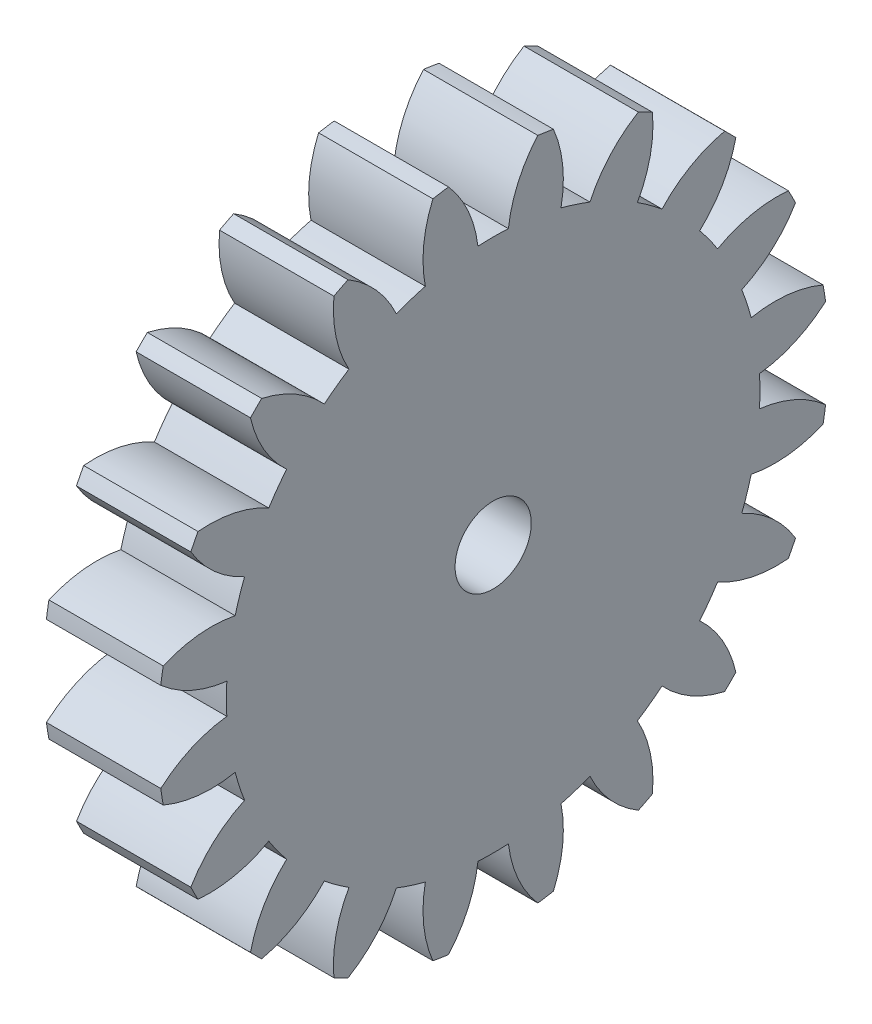
SolidWorks part; units mm, degrees
ref_plane "Plane1" through (0, 0, 0) normal (0, 0, 1) x (1, 0, 0)
ref_plane "Plane2" through (0, 0, 0) normal (0, 1, 0) x (1, 0, 0)
ref_plane "Plane3" through (0, 0, 0) normal (1, 0, 0) x (0, 0, -1)
sketch "HoldingSke" plane through (0, 0, 0) normal (0, 1, 0) x (1, 0, 0)
  line L0 (0, 0) -> (119.341, -43.4366)
  line L1 (-15, 0) -> (100, 0) construction
  line L2 (0, 0) -> (-2.1039, 2.3779)
  line L3 (0, 0) -> (-11.863, 4.5341)
  line L4 (0, 0) -> (8.1152, 2.9537)
  line L5 (0, 0) -> (-47.5972, -17.7524)
  line L6 (0, 0) -> (-15.7917, -10.6547)
  line L7 (-2.1039, 2.3779) -> (8.8308, 51.9871)
  line L8 (-76.2, 54.61) -> (-61.976, 54.61)
  line L9 (-71.009, 38.7566) -> (-53.1078, 45.2721)
  line L10 (-76.2, 71.12) -> (104.1128, 71.12)
  line L11 (0, 0) -> (-19.05, 0)
  line L12 (-76.2, 101.6) -> (-76.0095, 101.6)
  line L13 (24.9733, 27.94) -> (52.9518, 28.4284)
  line L14 (24.9733, 27.94) -> (24.9746, 27.94)
  line L15 (24.9733, 27.94) -> (100.4006, 29.5858)
  circle A0 centre (0, 0) radius 6.35
  circle A1 centre (0, 0) radius 38.1
  circle A2 centre (0, 0) radius 38.1
  circle A3 centre (0, 0) radius 6.35
  dimension "Num_teeth" = 20
  dimension "H" = 19.05
  dimension "Pitch_radius" = 180.3128
  dimension "Width" = 19.05
  dimension "Thickness" = 19.05
sketch "BasProSke" plane through (0, 0, 0) normal (0, 1, 0) x (1, 0, 0)
  line L0 (-10, 0) -> (60, 0) construction
  line L1 (0, 0) -> (0, 55.88)
  line L2 (0, 0) -> (19.05, 0)
  line L3 (19.05, 0) -> (19.05, 55.88)
  line L4 (19.05, 55.88) -> (0, 55.88)
  dimension "Thickness" = 19.05
  dimension "Diameter" = 111.76
revolve "Base-Revolve" add sketch "BasProSke" angle 360 about L0
sketch "TooCutSke" plane through (0, 0, 0) normal (1, 0, 0) x (0, 0, -1)
  line L1 (0, 0) -> (0, 107) construction
  line L2 (0, 0) -> (-4.3189, 50.6161) construction
  line L3 (0, 0) -> (-15.8526, 100.0894) construction
  line L4 (-4.3189, 50.6161) -> (-7.9263, 50.0447) construction
  arc A0 (2.5362, 44.3763) -> (-2.5362, 44.3763) centre (0, 0) ccw
  arc A1 (7.4573, 55.4058) -> (-7.4573, 55.4058) centre (0, 0) ccw
  circle A2 centre (0, 0) radius 50.8 construction
  circle A3 centre (0, 0) radius 47.7364 construction
  arc A4 (-2.5362, 44.3763) -> (-7.4573, 55.4058) centre (-22.715, 41.9856) ccw
  arc A5 (7.4573, 55.4058) -> (2.5362, 44.3763) centre (22.715, 41.9856) ccw
extrude "ToothCut" cut sketch "TooCutSke" along normal through all
fillet "Breaks" [suppressed] radius 0.1016 tangent propagation no
fillet "RootFillets" [suppressed] radius 1.2713
pattern_circular "TeethCuts" count 20 every 18 about axis through (-10, 0, 0) along (1, 0, 0) of "ToothCut", "RootFillets", "Breaks"
sketch "HubNeaOneSke" plane through (0, 0, 0) normal (-1, 0, 0) x (0, 0, 1)
  circle A0 centre (0, 0) radius 38.1
  dimension "Diameter" = 76.2
extrude "HubNearOne" [suppressed] add sketch "HubNeaOneSke" along normal blind 31.7501
sketch "HubNeaBotSke" plane through (0, 0, 0) normal (-1, 0, 0) x (0, 0, 1)
  circle A0 centre (0, 0) radius 38.1
  dimension "Diameter" = 76.2
extrude "HubNearBoth" [suppressed] add sketch "HubNeaBotSke" along normal blind 15.875
ref_plane "FarPln" through (19.05, 0, 0) normal (1, 0, 0) x (0, 0, -1)
sketch "HubFarSke" plane through (19.05, 0, 0) normal (1, 0, 0) x (0, 0, -1)
  circle A0 centre (0, 0) radius 38.1
  dimension "Diameter" = 76.2
extrude "HubFar" [suppressed] add sketch "HubFarSke" along normal blind 15.875
sketch "BorSke" plane through (0, 0, 0) normal (1, 0, 0) x (0, 0, -1)
  circle A0 centre (0, 0) radius 6.35
  dimension "Diameter" = 12.7
extrude "Bore" cut sketch "BorSke" along normal mid plane 101.6001
sketch "KeySke" plane through (0, 0, 0) normal (1, 0, 0) x (0, 0, -1)
  line L0 (-1.5875, 0) -> (-1.5875, 7.874)
  line L1 (-1.5875, 7.874) -> (1.5875, 7.874)
  line L2 (1.5875, 7.874) -> (1.5875, 0)
  line L3 (0, 0) -> (0, 34) construction
  line L4 (-1.5875, 0) -> (1.5875, 0)
  dimension "Width" = 3.175
extrude "Keyway" [suppressed] cut sketch "KeySke" along normal mid plane 101.6001
pattern_circular "Keyway2" [suppressed] count 2 every 90 about axis through (-10, 0, 0) along (1, 0, 0) reverse direction yes
equation "' \"Pitch@HoldingSke\" = 4"
equation "' \"Num_teeth@HoldingSke\" = 12"
equation "' \"Ap@HoldingSke\" =  20"
equation "' \"Ap@HoldingSke\" = 20"
equation "' \"Width@HoldingSke\" = 0.5"
equation "' \"Hub_dia@HoldingSke\"= 1"
equation "' \"Hub_dia@HoldingSke\" = 1"
equation "' \"Overall_len@HoldingSke\" = 1.0"
equation "' \"Bore@HoldingSke\" = 0.75"
equation "' \"T_dim@HoldingSke\" = 0.85"
equation "' \"Width@KeySke\" = 0.25"
equation "' \"Show_teeth@HoldingSke\" = 13"
equation "' \"Backlash@HoldingSke\" = 0.009"
equation "' \"Addendum_fac@HoldingSke\" = 1.0"
equation "' \"Dedendum_fac@HoldingSke\" = 1.25"
equation "' \"Dedendum_add@HoldingSke\" = 0.00005"
equation "' \"Clearance_fac@HoldingSke\" = 0.25"
equation "' \"Pitch@HoldingSke\" = 0.5"
equation "' \"Num_teeth@HoldingSke\" = 23"
equation "' \"Show_teeth@HoldingSke\" = 23"
equation "' \"Backlash@HoldingSke\" = 0.0375"
equation "\"Overcut_dia@TooCutSke\" = (\"Num_teeth@HoldingSke\" + 2 * \"Addendum_fac@HoldingSke\") / \"Pitch@HoldingSke\" + 0.002"
equation "\"Pitch_dia@TooCutSke\" = \"Num_teeth@HoldingSke\" / \"Pitch@HoldingSke\""
equation "\"Base_dia@TooCutSke\" = \"Num_teeth@HoldingSke\" / \"Pitch@HoldingSke\" * cos((\"Ap@HoldingSke\"  * 3.14159265 / 180))"
equation "\"Root_dia@TooCutSke\" = (\"Num_teeth@HoldingSke\" + 2) / \"Pitch@HoldingSke\" - 2 * (\"Addendum_fac@HoldingSke\" + \"Dedendum_fac@HoldingSke\") / \"Pitch@HoldingSke\" - \"Dedendum_add@HoldingSke\" * 2"
equation "\"Half_ang@TooCutSke\" = 180 / \"Num_teeth@HoldingSke\""
equation "\"Half_CT@TooCutSke\" = \"Num_teeth@HoldingSke\" / \"Pitch@HoldingSke\" * sin((3.14159265 / 2 / \"Num_teeth@HoldingSke\")) / 2 - 7 * \"Backlash@HoldingSke\" / 4"
equation "\"Flank_rad@TooCutSke\" = \"Num_teeth@HoldingSke\" / \"Pitch@HoldingSke\" / 5"
equation "\"Radius@RootFillets\" = \"Clearance_fac@HoldingSke\" / \"Pitch@HoldingSke\" + \"Dedendum_add@HoldingSke\""
equation "\"Break_rad@Breaks\" = 0.02 / \"Pitch@HoldingSke\""
equation "\"Thickness@HoldingSke\" = \"Width@HoldingSke\""
equation "\"OAL@HoldingSke\" = \"Thickness@HoldingSke\""
equation "\"MHD@HoldingSke\" = (\"Num_teeth@HoldingSke\" + 2) / \"Pitch@HoldingSke\" - 2 * (\"Addendum_fac@HoldingSke\" + \"Dedendum_fac@HoldingSke\")  / \"Pitch@HoldingSke\" - \"Dedendum_add@HoldingSke\" * 2"
equation "\"MBD@HoldingSke\" = (\"Num_teeth@HoldingSke\" + 2) / \"Pitch@HoldingSke\" - 2 * (\"Addendum_fac@HoldingSke\" + \"Dedendum_fac@HoldingSke\")  / \"Pitch@HoldingSke\" - \"Dedendum_add@HoldingSke\" * 2 - 0.002"
equation "\"MHD@HoldingSke\" = ((sgn( \"MHD@HoldingSke\" - \"Hub_dia@HoldingSke\" )-1)*( \"MHD@HoldingSke\" - \"Hub_dia@HoldingSke\" ))/-2+ \"Hub_dia@HoldingSke\""
equation "\"MBD@HoldingSke\" = ((sgn( \"MBD@HoldingSke\" - \"Bore@HoldingSke\" )-1)*( \"MBD@HoldingSke\" - \"Bore@HoldingSke\" ))/-2+ \"Bore@HoldingSke\""
equation "\"OAL@HoldingSke\" = ((sgn( \"OAL@HoldingSke\" - \"Overall_len@HoldingSke\" )+1)*( \"OAL@HoldingSke\" - \"Overall_len@HoldingSke\" ))/2 + \"Overall_len@HoldingSke\" + 0.000002"
equation "\"Num_teeth@TeethCuts\" = int( \"Show_teeth@HoldingSke\" ) + 1"
equation "\"Num_teeth@TeethCuts\" = ((sgn( \"Num_teeth@TeethCuts\" - \"Num_teeth@HoldingSke\" )-1)*( \"Num_teeth@TeethCuts\" - \"Num_teeth@HoldingSke\" ))/-2+ \"Num_teeth@HoldingSke\""
equation "\"Num_teeth@TeethCuts\" = ((sgn( \"Num_teeth@TeethCuts\" - 2.0)+1)*( \"Num_teeth@TeethCuts\" - 2.0))/2 +2.0"
equation "\"Angle@TeethCuts\" = 360.0 / \"Num_teeth@HoldingSke\""
equation "\"Diameter@BasProSke\" = (\"Num_teeth@HoldingSke\" + 2 * \"Addendum_fac@HoldingSke\") / \"Pitch@HoldingSke\""
equation "\"Thickness@BasProSke\"  = \"Thickness@HoldingSke\""
equation "' \"Fillet_rad@BasProSke\" =  \"Thickness@HoldingSke\" * 0.05"
equation "' \"Fillet_rad@BasProSke\" = \"Thickness@HoldingSke\" * 0.05"
equation "\"MHD@HoldingSke\" = ((sgn( \"MHD@HoldingSke\" - \"Root_dia@TooCutSke\" )-1)*( \"MHD@HoldingSke\" - \"Root_dia@TooCutSke\" ))/-2+ \"Root_dia@TooCutSke\""
equation "\"Diameter@HubNeaOneSke\" = \"MHD@HoldingSke\""
equation "\"Length@HubNearOne\" = \"OAL@HoldingSke\" - \"Thickness@BasProSke\""
equation "\"Diameter@HubNeaBotSke\" = \"MHD@HoldingSke\""
equation "\"Length@HubNearBoth\" = ( \"OAL@HoldingSke\" - \"Thickness@BasProSke\" ) / 2.0"
equation "\"Thickness@FarPln\" = \"Thickness@BasProSke\""
equation "\"Diameter@HubFarSke\" = \"MHD@HoldingSke\""
equation "\"Length@HubFar\" = ( \"OAL@HoldingSke\" - \"Thickness@BasProSke\" ) / 2.0"
equation "\"Diameter@BorSke\" = \"MBD@HoldingSke\""
equation "\"D1@Bore\" = \"OAL@HoldingSke\" * 2.0"
equation "\"D1@Keyway\" = \"OAL@HoldingSke\" * 2.0"
equation "\"Offset@KeySke\" = \"T_dim@HoldingSke\" - \"MBD@HoldingSke\" / 2.0"
